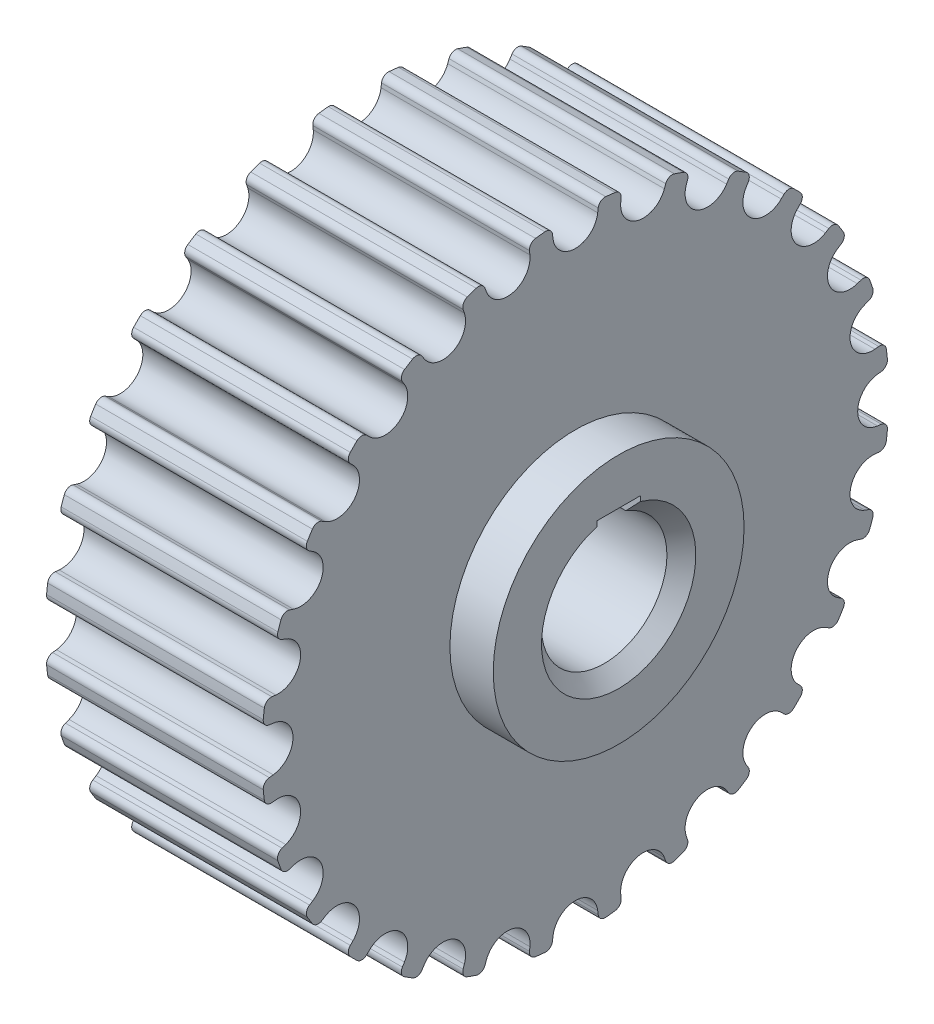
SolidWorks part; units mm, degrees
ref_plane "前视基准面" through (0, 0, 0) normal (0, 0, 1) x (1, 0, 0)
ref_plane "上视基准面" through (0, 0, 0) normal (0, 1, 0) x (1, 0, 0)
ref_plane "右视基准面" through (0, 0, 0) normal (1, 0, 0) x (0, 0, -1)
sketch "草图1" plane through (0, 0, 0) normal (0, 0, 1) x (1, 0, 0)
  line L0 (0, 0) -> (64.8368, 0) construction
  line L1 (0, 4.3416) -> (0, 21.708)
  line L2 (0, 21.708) -> (15, 21.708)
  line L3 (15, 21.708) -> (15, 8.6832)
  line L4 (15, 8.6832) -> (18, 8.6832)
  line L5 (18, 8.6832) -> (18, 4.3416)
  line L6 (18, 4.3416) -> (0, 4.3416)
  dimension "L" = 18
  dimension "B" = 15
  dimension "d" = 8.6832
  dimension "d1" = 17.3664
  dimension "da" = 43.416
revolve "旋转1" add sketch "草图1" angle 360 about L0
chamfer "倒角1" distance 1 angle 45 2 edges at (18, 0, 4.3416) (0, 0, 4.3416)
sketch "草图4" plane through (0, 0, 0) normal (-1, 0, 0) x (0, 0, 1)
  line L1 (-1.5, 4.0742) -> (1.5, 4.0742)
  line L2 (-1.5, 4.0742) -> (-1.5, 5.4742)
  line L3 (-1.5, 5.4742) -> (1.5, 5.4742)
  line L4 (1.5, 4.0742) -> (1.5, 5.4742)
  circle A0 centre (0, 0) radius 4.3416 construction
  dimension "键槽宽度" = 3
  dimension "t1" = 1.4
extrude "切除-拉伸1" cut sketch "草图4" against normal through all
ref_axis "基准轴1" through (-1.4, 0, 0) along (1, 0, 0)
sketch "草图6" plane through (0, 0, 0) normal (1, 0, 0) x (0, 0, -1)
  line L0 (0, 0) -> (0, 30.6512) construction
  line L1 (1.5814, 21.1865) -> (1.5484, 20.9179)
  line L2 (2.5815, 21.554) -> (2.7782, 23.1555)
  line L3 (-2.5815, 21.554) -> (-2.7782, 23.1555)
  line L4 (-1.5814, 21.1865) -> (-1.5484, 20.9179)
  circle A0 centre (0, 0) radius 21.708 construction
  circle A1 centre (0, 0) radius 19.548 construction
  arc A2 (-1.5484, 20.9179) -> (1.5484, 20.9179) centre (0, 21.108) ccw
  arc A3 (2.7782, 23.1555) -> (-2.7782, 23.1555) centre (0, 0) ccw
  arc A4 (1.5814, 21.1865) -> (2.1043, 21.6058) centre (2.0578, 21.128) cw
  arc A5 (2.1043, 21.6058) -> (2.5815, 21.554) centre (0, 0) cw
  arc A6 (-2.1043, 21.6058) -> (-2.5815, 21.554) centre (0, 0) ccw
  arc A7 (-1.5814, 21.1865) -> (-2.1043, 21.6058) centre (-2.0578, 21.128) ccw
  point P7 (0, 3.25)
  point P8 (0, 28.4912)
  point P15 (1.6378, 21.6461)
  dimension "D1" = 39.096
  dimension "ra" = 0.48
  dimension "rf" = 1.56
  dimension "hg" = 2.16
  dimension "D3" = 0.48
  dimension "D4" = 1.6136
  dimension "angle" = 14
  dimension "bw" = 3.25
extrude "切除-拉伸2" cut sketch "草图6" along normal up to next
pattern_circular "阵列(圆周)3" count 28 over 360 about axis through (-1.4, 0, 0) along (1, 0, 0) of "切除-拉伸2"
ref_plane "基准面1" through (45, 0, 0) normal (1, 0, 0) x (0, 0, -1)
sketch "草图7" plane through (45, 0, 0) normal (1, 0, 0) x (0, 0, -1)
  line L56 (1.5814, 21.1865) -> (1.5484, 20.9179)
  line L57 (-1.5484, 20.9179) -> (-1.5814, 21.1865)
  line L58 (-3.1727, 21.0072) -> (-3.1451, 20.738)
  line L59 (-6.1642, 20.0489) -> (-6.2562, 20.3034)
  line L60 (-7.7677, 19.7745) -> (-7.6809, 19.5182)
  line L61 (-10.471, 18.1745) -> (-10.6172, 18.4023)
  line L62 (-11.9732, 17.5503) -> (-11.8315, 17.3197)
  line L63 (-14.2527, 15.3889) -> (-14.4459, 15.5783)
  line L64 (-15.5783, 14.4459) -> (-15.3889, 14.2527)
  line L65 (-17.3197, 11.8315) -> (-17.5503, 11.9732)
  line L66 (-18.4023, 10.6172) -> (-18.1745, 10.471)
  line L67 (-19.5182, 7.6809) -> (-19.7745, 7.7677)
  line L68 (-20.3034, 6.2562) -> (-20.0489, 6.1642)
  line L69 (-20.738, 3.1451) -> (-21.0072, 3.1727)
  line L70 (-21.1865, 1.5814) -> (-20.9179, 1.5484)
  line L71 (-20.9179, -1.5484) -> (-21.1865, -1.5814)
  line L72 (-21.0072, -3.1727) -> (-20.738, -3.1451)
  line L73 (-20.0489, -6.1642) -> (-20.3034, -6.2562)
  line L74 (-19.7745, -7.7677) -> (-19.5182, -7.6809)
  line L75 (-18.1745, -10.471) -> (-18.4023, -10.6172)
  line L76 (-17.5503, -11.9732) -> (-17.3197, -11.8315)
  line L77 (-15.3889, -14.2527) -> (-15.5783, -14.4459)
  line L78 (-14.4459, -15.5783) -> (-14.2527, -15.3889)
  line L79 (-11.8315, -17.3197) -> (-11.9732, -17.5503)
  line L80 (-10.6172, -18.4023) -> (-10.471, -18.1745)
  line L81 (-7.6809, -19.5182) -> (-7.7677, -19.7745)
  line L82 (-6.2562, -20.3034) -> (-6.1642, -20.0489)
  line L83 (-3.1451, -20.738) -> (-3.1727, -21.0072)
  line L84 (-1.5814, -21.1865) -> (-1.5484, -20.9179)
  line L85 (1.5484, -20.9179) -> (1.5814, -21.1865)
  line L86 (3.1727, -21.0072) -> (3.1451, -20.738)
  line L87 (6.1642, -20.0489) -> (6.2562, -20.3034)
  line L88 (7.7677, -19.7745) -> (7.6809, -19.5182)
  line L89 (10.471, -18.1745) -> (10.6172, -18.4023)
  line L90 (11.9732, -17.5503) -> (11.8315, -17.3197)
  line L91 (14.2527, -15.3889) -> (14.4459, -15.5783)
  line L92 (15.5783, -14.4459) -> (15.3889, -14.2527)
  line L93 (17.3197, -11.8315) -> (17.5503, -11.9732)
  line L94 (18.4023, -10.6172) -> (18.1745, -10.471)
  line L95 (19.5182, -7.6809) -> (19.7745, -7.7677)
  line L96 (20.3034, -6.2562) -> (20.0489, -6.1642)
  line L97 (20.738, -3.1451) -> (21.0072, -3.1727)
  line L98 (21.1865, -1.5814) -> (20.9179, -1.5484)
  line L99 (20.9179, 1.5484) -> (21.1865, 1.5814)
  line L100 (21.0072, 3.1727) -> (20.738, 3.1451)
  line L101 (20.0489, 6.1642) -> (20.3034, 6.2562)
  line L102 (19.7745, 7.7677) -> (19.5182, 7.6809)
  line L103 (18.1745, 10.471) -> (18.4023, 10.6172)
  line L104 (17.5503, 11.9732) -> (17.3197, 11.8315)
  line L105 (15.3889, 14.2527) -> (15.5783, 14.4459)
  line L106 (14.4459, 15.5783) -> (14.2527, 15.3889)
  line L107 (11.8315, 17.3197) -> (11.9732, 17.5503)
  line L108 (10.6172, 18.4023) -> (10.471, 18.1745)
  line L109 (7.6809, 19.5182) -> (7.7677, 19.7745)
  line L110 (6.2562, 20.3034) -> (6.1642, 20.0489)
  line L111 (3.1451, 20.738) -> (3.1727, 21.0072)
  line L112 (1.5814, 21.1865) -> (1.5484, 20.9179)
  line L113 (-1.5484, 20.9179) -> (-1.5814, 21.1865)
  line L114 (-3.1727, 21.0072) -> (-3.1451, 20.738)
  line L115 (-6.1642, 20.0489) -> (-6.2562, 20.3034)
  line L116 (-7.7677, 19.7745) -> (-7.6809, 19.5182)
  line L117 (-10.471, 18.1745) -> (-10.6172, 18.4023)
  line L118 (-11.9732, 17.5503) -> (-11.8315, 17.3197)
  line L119 (-14.2527, 15.3889) -> (-14.4459, 15.5783)
  line L120 (-15.5783, 14.4459) -> (-15.3889, 14.2527)
  line L121 (-17.3197, 11.8315) -> (-17.5503, 11.9732)
  line L122 (-18.4023, 10.6172) -> (-18.1745, 10.471)
  line L123 (-19.5182, 7.6809) -> (-19.7745, 7.7677)
  line L124 (-20.3034, 6.2562) -> (-20.0489, 6.1642)
  line L125 (-20.738, 3.1451) -> (-21.0072, 3.1727)
  line L126 (-21.1865, 1.5814) -> (-20.9179, 1.5484)
  line L127 (-20.9179, -1.5484) -> (-21.1865, -1.5814)
  line L128 (-21.0072, -3.1727) -> (-20.738, -3.1451)
  line L129 (-20.0489, -6.1642) -> (-20.3034, -6.2562)
  line L130 (-19.7745, -7.7677) -> (-19.5182, -7.6809)
  line L131 (-18.1745, -10.471) -> (-18.4023, -10.6172)
  line L132 (-17.5503, -11.9732) -> (-17.3197, -11.8315)
  line L133 (-15.3889, -14.2527) -> (-15.5783, -14.4459)
  line L134 (-14.4459, -15.5783) -> (-14.2527, -15.3889)
  line L135 (-11.8315, -17.3197) -> (-11.9732, -17.5503)
  line L136 (-10.6172, -18.4023) -> (-10.471, -18.1745)
  line L137 (-7.6809, -19.5182) -> (-7.7677, -19.7745)
  line L138 (-6.2562, -20.3034) -> (-6.1642, -20.0489)
  line L139 (-3.1451, -20.738) -> (-3.1727, -21.0072)
  line L140 (-1.5814, -21.1865) -> (-1.5484, -20.9179)
  line L141 (1.5484, -20.9179) -> (1.5814, -21.1865)
  line L142 (3.1727, -21.0072) -> (3.1451, -20.738)
  line L143 (6.1642, -20.0489) -> (6.2562, -20.3034)
  line L144 (7.7677, -19.7745) -> (7.6809, -19.5182)
  line L145 (10.471, -18.1745) -> (10.6172, -18.4023)
  line L146 (11.9732, -17.5503) -> (11.8315, -17.3197)
  line L147 (14.2527, -15.3889) -> (14.4459, -15.5783)
  line L148 (15.5783, -14.4459) -> (15.3889, -14.2527)
  line L149 (17.3197, -11.8315) -> (17.5503, -11.9732)
  line L150 (18.4023, -10.6172) -> (18.1745, -10.471)
  line L151 (19.5182, -7.6809) -> (19.7745, -7.7677)
  line L152 (20.3034, -6.2562) -> (20.0489, -6.1642)
  line L153 (20.738, -3.1451) -> (21.0072, -3.1727)
  line L154 (21.1865, -1.5814) -> (20.9179, -1.5484)
  line L155 (20.9179, 1.5484) -> (21.1865, 1.5814)
  line L156 (21.0072, 3.1727) -> (20.738, 3.1451)
  line L157 (20.0489, 6.1642) -> (20.3034, 6.2562)
  line L158 (19.7745, 7.7677) -> (19.5182, 7.6809)
  line L159 (18.1745, 10.471) -> (18.4023, 10.6172)
  line L160 (17.5503, 11.9732) -> (17.3197, 11.8315)
  line L161 (15.3889, 14.2527) -> (15.5783, 14.4459)
  line L162 (14.4459, 15.5783) -> (14.2527, 15.3889)
  line L163 (11.8315, 17.3197) -> (11.9732, 17.5503)
  line L164 (10.6172, 18.4023) -> (10.471, 18.1745)
  line L165 (7.6809, 19.5182) -> (7.7677, 19.7745)
  line L166 (6.2562, 20.3034) -> (6.1642, 20.0489)
  line L167 (3.1451, 20.738) -> (3.1727, 21.0072)
  arc A112 (3.1727, 21.0072) -> (2.7562, 21.5323) centre (2.6952, 21.0562) ccw
  arc A113 (2.7562, 21.5323) -> (2.1043, 21.6058) centre (0, 0) ccw
  arc A114 (2.1043, 21.6058) -> (1.5814, 21.1865) centre (2.0578, 21.128) ccw
  arc A115 (-1.5484, 20.9179) -> (1.5484, 20.9179) centre (0, 21.108) ccw
  arc A116 (-1.5814, 21.1865) -> (-2.1043, 21.6058) centre (-2.0578, 21.128) ccw
  arc A117 (-2.1043, 21.6058) -> (-2.7562, 21.5323) centre (0, 0) ccw
  arc A118 (-2.7562, 21.5323) -> (-3.1727, 21.0072) centre (-2.6952, 21.0562) ccw
  arc A119 (-6.1642, 20.0489) -> (-3.1451, 20.738) centre (-4.697, 20.5788) ccw
  arc A120 (-6.2562, 20.3034) -> (-6.8593, 20.5958) centre (-6.7076, 20.1404) ccw
  arc A121 (-6.8593, 20.5958) -> (-7.4785, 20.3791) centre (0, 0) ccw
  arc A122 (-7.4785, 20.3791) -> (-7.7677, 19.7745) centre (-7.3131, 19.9285) ccw
  arc A123 (-10.471, 18.1745) -> (-7.6809, 19.5182) centre (-9.1584, 19.0177) ccw
  arc A124 (-10.6172, 18.4023) -> (-11.2703, 18.5531) centre (-11.0211, 18.1429) ccw
  arc A125 (-11.2703, 18.5531) -> (-11.8258, 18.2041) centre (0, 0) ccw
  arc A126 (-11.8258, 18.2041) -> (-11.9732, 17.5503) centre (-11.5643, 17.8016) ccw
  arc A127 (-14.2527, 15.3889) -> (-11.8315, 17.3197) centre (-13.1606, 16.5029) ccw
  arc A128 (-14.4459, 15.5783) -> (-15.1162, 15.5801) centre (-14.7819, 15.2356) ccw
  arc A129 (-15.1162, 15.5801) -> (-15.5801, 15.1162) centre (0, 0) ccw
  arc A130 (-15.5801, 15.1162) -> (-15.5783, 14.4459) centre (-15.2356, 14.7819) ccw
  arc A131 (-17.3197, 11.8315) -> (-15.3889, 14.2527) centre (-16.5029, 13.1606) ccw
  arc A132 (-17.5503, 11.9732) -> (-18.2041, 11.8258) centre (-17.8016, 11.5643) ccw
  arc A133 (-18.2041, 11.8258) -> (-18.5531, 11.2703) centre (0, 0) ccw
  arc A134 (-18.5531, 11.2703) -> (-18.4023, 10.6172) centre (-18.1429, 11.0211) ccw
  arc A135 (-19.5182, 7.6809) -> (-18.1745, 10.471) centre (-19.0177, 9.1584) ccw
  arc A136 (-19.7745, 7.7677) -> (-20.3791, 7.4785) centre (-19.9285, 7.3131) ccw
  arc A137 (-20.3791, 7.4785) -> (-20.5958, 6.8593) centre (0, 0) ccw
  arc A138 (-20.5958, 6.8593) -> (-20.3034, 6.2562) centre (-20.1404, 6.7076) ccw
  arc A139 (-20.738, 3.1451) -> (-20.0489, 6.1642) centre (-20.5788, 4.697) ccw
  arc A140 (-21.0072, 3.1727) -> (-21.5323, 2.7562) centre (-21.0562, 2.6952) ccw
  arc A141 (-21.5323, 2.7562) -> (-21.6058, 2.1043) centre (0, 0) ccw
  arc A142 (-21.6058, 2.1043) -> (-21.1865, 1.5814) centre (-21.128, 2.0578) ccw
  arc A143 (-20.9179, -1.5484) -> (-20.9179, 1.5484) centre (-21.108, 0) ccw
  arc A144 (-21.1865, -1.5814) -> (-21.6058, -2.1043) centre (-21.128, -2.0578) ccw
  arc A145 (-21.6058, -2.1043) -> (-21.5323, -2.7562) centre (0, 0) ccw
  arc A146 (-21.5323, -2.7562) -> (-21.0072, -3.1727) centre (-21.0562, -2.6952) ccw
  arc A147 (-20.0489, -6.1642) -> (-20.738, -3.1451) centre (-20.5788, -4.697) ccw
  arc A148 (-20.3034, -6.2562) -> (-20.5958, -6.8593) centre (-20.1404, -6.7076) ccw
  arc A149 (-20.5958, -6.8593) -> (-20.3791, -7.4785) centre (0, 0) ccw
  arc A150 (-20.3791, -7.4785) -> (-19.7745, -7.7677) centre (-19.9285, -7.3131) ccw
  arc A151 (-18.1745, -10.471) -> (-19.5182, -7.6809) centre (-19.0177, -9.1584) ccw
  arc A152 (-18.4023, -10.6172) -> (-18.5531, -11.2703) centre (-18.1429, -11.0211) ccw
  arc A153 (-18.5531, -11.2703) -> (-18.2041, -11.8258) centre (0, 0) ccw
  arc A154 (-18.2041, -11.8258) -> (-17.5503, -11.9732) centre (-17.8016, -11.5643) ccw
  arc A155 (-15.3889, -14.2527) -> (-17.3197, -11.8315) centre (-16.5029, -13.1606) ccw
  arc A156 (-15.5783, -14.4459) -> (-15.5801, -15.1162) centre (-15.2356, -14.7819) ccw
  arc A157 (-15.5801, -15.1162) -> (-15.1162, -15.5801) centre (0, 0) ccw
  arc A158 (-15.1162, -15.5801) -> (-14.4459, -15.5783) centre (-14.7819, -15.2356) ccw
  arc A159 (-11.8315, -17.3197) -> (-14.2527, -15.3889) centre (-13.1606, -16.5029) ccw
  arc A160 (-11.9732, -17.5503) -> (-11.8258, -18.2041) centre (-11.5643, -17.8016) ccw
  arc A161 (-11.8258, -18.2041) -> (-11.2703, -18.5531) centre (0, 0) ccw
  arc A162 (-11.2703, -18.5531) -> (-10.6172, -18.4023) centre (-11.0211, -18.1429) ccw
  arc A163 (-7.6809, -19.5182) -> (-10.471, -18.1745) centre (-9.1584, -19.0177) ccw
  arc A164 (-7.7677, -19.7745) -> (-7.4785, -20.3791) centre (-7.3131, -19.9285) ccw
  arc A165 (-7.4785, -20.3791) -> (-6.8593, -20.5958) centre (0, 0) ccw
  arc A166 (-6.8593, -20.5958) -> (-6.2562, -20.3034) centre (-6.7076, -20.1404) ccw
  arc A167 (-3.1451, -20.738) -> (-6.1642, -20.0489) centre (-4.697, -20.5788) ccw
  arc A168 (-3.1727, -21.0072) -> (-2.7562, -21.5323) centre (-2.6952, -21.0562) ccw
  arc A169 (-2.7562, -21.5323) -> (-2.1043, -21.6058) centre (0, 0) ccw
  arc A170 (-2.1043, -21.6058) -> (-1.5814, -21.1865) centre (-2.0578, -21.128) ccw
  arc A171 (1.5484, -20.9179) -> (-1.5484, -20.9179) centre (0, -21.108) ccw
  arc A172 (1.5814, -21.1865) -> (2.1043, -21.6058) centre (2.0578, -21.128) ccw
  arc A173 (2.1043, -21.6058) -> (2.7562, -21.5323) centre (0, 0) ccw
  arc A174 (2.7562, -21.5323) -> (3.1727, -21.0072) centre (2.6952, -21.0562) ccw
  arc A175 (6.1642, -20.0489) -> (3.1451, -20.738) centre (4.697, -20.5788) ccw
  arc A176 (6.2562, -20.3034) -> (6.8593, -20.5958) centre (6.7076, -20.1404) ccw
  arc A177 (6.8593, -20.5958) -> (7.4785, -20.3791) centre (0, 0) ccw
  arc A178 (7.4785, -20.3791) -> (7.7677, -19.7745) centre (7.3131, -19.9285) ccw
  arc A179 (10.471, -18.1745) -> (7.6809, -19.5182) centre (9.1584, -19.0177) ccw
  arc A180 (10.6172, -18.4023) -> (11.2703, -18.5531) centre (11.0211, -18.1429) ccw
  arc A181 (11.2703, -18.5531) -> (11.8258, -18.2041) centre (0, 0) ccw
  arc A182 (11.8258, -18.2041) -> (11.9732, -17.5503) centre (11.5643, -17.8016) ccw
  arc A183 (14.2527, -15.3889) -> (11.8315, -17.3197) centre (13.1606, -16.5029) ccw
  arc A184 (14.4459, -15.5783) -> (15.1162, -15.5801) centre (14.7819, -15.2356) ccw
  arc A185 (15.1162, -15.5801) -> (15.5801, -15.1162) centre (0, 0) ccw
  arc A186 (15.5801, -15.1162) -> (15.5783, -14.4459) centre (15.2356, -14.7819) ccw
  arc A187 (17.3197, -11.8315) -> (15.3889, -14.2527) centre (16.5029, -13.1606) ccw
  arc A188 (17.5503, -11.9732) -> (18.2041, -11.8258) centre (17.8016, -11.5643) ccw
  arc A189 (18.2041, -11.8258) -> (18.5531, -11.2703) centre (0, 0) ccw
  arc A190 (18.5531, -11.2703) -> (18.4023, -10.6172) centre (18.1429, -11.0211) ccw
  arc A191 (19.5182, -7.6809) -> (18.1745, -10.471) centre (19.0177, -9.1584) ccw
  arc A192 (19.7745, -7.7677) -> (20.3791, -7.4785) centre (19.9285, -7.3131) ccw
  arc A193 (20.3791, -7.4785) -> (20.5958, -6.8593) centre (0, 0) ccw
  arc A194 (20.5958, -6.8593) -> (20.3034, -6.2562) centre (20.1404, -6.7076) ccw
  arc A195 (20.738, -3.1451) -> (20.0489, -6.1642) centre (20.5788, -4.697) ccw
  arc A196 (21.0072, -3.1727) -> (21.5323, -2.7562) centre (21.0562, -2.6952) ccw
  arc A197 (21.5323, -2.7562) -> (21.6058, -2.1043) centre (0, 0) ccw
  arc A198 (21.6058, -2.1043) -> (21.1865, -1.5814) centre (21.128, -2.0578) ccw
  arc A199 (20.9179, 1.5484) -> (20.9179, -1.5484) centre (21.108, 0) ccw
  arc A200 (21.1865, 1.5814) -> (21.6058, 2.1043) centre (21.128, 2.0578) ccw
  arc A201 (21.6058, 2.1043) -> (21.5323, 2.7562) centre (0, 0) ccw
  arc A202 (21.5323, 2.7562) -> (21.0072, 3.1727) centre (21.0562, 2.6952) ccw
  arc A203 (20.0489, 6.1642) -> (20.738, 3.1451) centre (20.5788, 4.697) ccw
  arc A204 (20.3034, 6.2562) -> (20.5958, 6.8593) centre (20.1404, 6.7076) ccw
  arc A205 (20.5958, 6.8593) -> (20.3791, 7.4785) centre (0, 0) ccw
  arc A206 (20.3791, 7.4785) -> (19.7745, 7.7677) centre (19.9285, 7.3131) ccw
  arc A207 (18.1745, 10.471) -> (19.5182, 7.6809) centre (19.0177, 9.1584) ccw
  arc A208 (18.4023, 10.6172) -> (18.5531, 11.2703) centre (18.1429, 11.0211) ccw
  arc A209 (18.5531, 11.2703) -> (18.2041, 11.8258) centre (0, 0) ccw
  arc A210 (18.2041, 11.8258) -> (17.5503, 11.9732) centre (17.8016, 11.5643) ccw
  arc A211 (15.3889, 14.2527) -> (17.3197, 11.8315) centre (16.5029, 13.1606) ccw
  arc A212 (15.5783, 14.4459) -> (15.5801, 15.1162) centre (15.2356, 14.7819) ccw
  arc A213 (15.5801, 15.1162) -> (15.1162, 15.5801) centre (0, 0) ccw
  arc A214 (15.1162, 15.5801) -> (14.4459, 15.5783) centre (14.7819, 15.2356) ccw
  arc A215 (11.8315, 17.3197) -> (14.2527, 15.3889) centre (13.1606, 16.5029) ccw
  arc A216 (11.9732, 17.5503) -> (11.8258, 18.2041) centre (11.5643, 17.8016) ccw
  arc A217 (11.8258, 18.2041) -> (11.2703, 18.5531) centre (0, 0) ccw
  arc A218 (11.2703, 18.5531) -> (10.6172, 18.4023) centre (11.0211, 18.1429) ccw
  arc A219 (7.6809, 19.5182) -> (10.471, 18.1745) centre (9.1584, 19.0177) ccw
  arc A220 (7.7677, 19.7745) -> (7.4785, 20.3791) centre (7.3131, 19.9285) ccw
  arc A221 (7.4785, 20.3791) -> (6.8593, 20.5958) centre (0, 0) ccw
  arc A222 (6.8593, 20.5958) -> (6.2562, 20.3034) centre (6.7076, 20.1404) ccw
  arc A223 (3.1451, 20.738) -> (6.1642, 20.0489) centre (4.697, 20.5788) ccw
  arc A224 (3.1727, 21.0072) -> (2.7562, 21.5323) centre (2.6952, 21.0562) ccw
  arc A225 (2.7562, 21.5323) -> (2.1043, 21.6058) centre (0, 0) ccw
  arc A226 (2.1043, 21.6058) -> (1.5814, 21.1865) centre (2.0578, 21.128) ccw
  arc A227 (-1.5484, 20.9179) -> (1.5484, 20.9179) centre (0, 21.108) ccw
  arc A228 (-1.5814, 21.1865) -> (-2.1043, 21.6058) centre (-2.0578, 21.128) ccw
  arc A229 (-2.1043, 21.6058) -> (-2.7562, 21.5323) centre (0, 0) ccw
  arc A230 (-2.7562, 21.5323) -> (-3.1727, 21.0072) centre (-2.6952, 21.0562) ccw
  arc A231 (-6.1642, 20.0489) -> (-3.1451, 20.738) centre (-4.697, 20.5788) ccw
  arc A232 (-6.2562, 20.3034) -> (-6.8593, 20.5958) centre (-6.7076, 20.1404) ccw
  arc A233 (-6.8593, 20.5958) -> (-7.4785, 20.3791) centre (0, 0) ccw
  arc A234 (-7.4785, 20.3791) -> (-7.7677, 19.7745) centre (-7.3131, 19.9285) ccw
  arc A235 (-10.471, 18.1745) -> (-7.6809, 19.5182) centre (-9.1584, 19.0177) ccw
  arc A236 (-10.6172, 18.4023) -> (-11.2703, 18.5531) centre (-11.0211, 18.1429) ccw
  arc A237 (-11.2703, 18.5531) -> (-11.8258, 18.2041) centre (0, 0) ccw
  arc A238 (-11.8258, 18.2041) -> (-11.9732, 17.5503) centre (-11.5643, 17.8016) ccw
  arc A239 (-14.2527, 15.3889) -> (-11.8315, 17.3197) centre (-13.1606, 16.5029) ccw
  arc A240 (-14.4459, 15.5783) -> (-15.1162, 15.5801) centre (-14.7819, 15.2356) ccw
  arc A241 (-15.1162, 15.5801) -> (-15.5801, 15.1162) centre (0, 0) ccw
  arc A242 (-15.5801, 15.1162) -> (-15.5783, 14.4459) centre (-15.2356, 14.7819) ccw
  arc A243 (-17.3197, 11.8315) -> (-15.3889, 14.2527) centre (-16.5029, 13.1606) ccw
  arc A244 (-17.5503, 11.9732) -> (-18.2041, 11.8258) centre (-17.8016, 11.5643) ccw
  arc A245 (-18.2041, 11.8258) -> (-18.5531, 11.2703) centre (0, 0) ccw
  arc A246 (-18.5531, 11.2703) -> (-18.4023, 10.6172) centre (-18.1429, 11.0211) ccw
  arc A247 (-19.5182, 7.6809) -> (-18.1745, 10.471) centre (-19.0177, 9.1584) ccw
  arc A248 (-19.7745, 7.7677) -> (-20.3791, 7.4785) centre (-19.9285, 7.3131) ccw
  arc A249 (-20.3791, 7.4785) -> (-20.5958, 6.8593) centre (0, 0) ccw
  arc A250 (-20.5958, 6.8593) -> (-20.3034, 6.2562) centre (-20.1404, 6.7076) ccw
  arc A251 (-20.738, 3.1451) -> (-20.0489, 6.1642) centre (-20.5788, 4.697) ccw
  arc A252 (-21.0072, 3.1727) -> (-21.5323, 2.7562) centre (-21.0562, 2.6952) ccw
  arc A253 (-21.5323, 2.7562) -> (-21.6058, 2.1043) centre (0, 0) ccw
  arc A254 (-21.6058, 2.1043) -> (-21.1865, 1.5814) centre (-21.128, 2.0578) ccw
  arc A255 (-20.9179, -1.5484) -> (-20.9179, 1.5484) centre (-21.108, 0) ccw
  arc A256 (-21.1865, -1.5814) -> (-21.6058, -2.1043) centre (-21.128, -2.0578) ccw
  arc A257 (-21.6058, -2.1043) -> (-21.5323, -2.7562) centre (0, 0) ccw
  arc A258 (-21.5323, -2.7562) -> (-21.0072, -3.1727) centre (-21.0562, -2.6952) ccw
  arc A259 (-20.0489, -6.1642) -> (-20.738, -3.1451) centre (-20.5788, -4.697) ccw
  arc A260 (-20.3034, -6.2562) -> (-20.5958, -6.8593) centre (-20.1404, -6.7076) ccw
  arc A261 (-20.5958, -6.8593) -> (-20.3791, -7.4785) centre (0, 0) ccw
  arc A262 (-20.3791, -7.4785) -> (-19.7745, -7.7677) centre (-19.9285, -7.3131) ccw
  arc A263 (-18.1745, -10.471) -> (-19.5182, -7.6809) centre (-19.0177, -9.1584) ccw
  arc A264 (-18.4023, -10.6172) -> (-18.5531, -11.2703) centre (-18.1429, -11.0211) ccw
  arc A265 (-18.5531, -11.2703) -> (-18.2041, -11.8258) centre (0, 0) ccw
  arc A266 (-18.2041, -11.8258) -> (-17.5503, -11.9732) centre (-17.8016, -11.5643) ccw
  arc A267 (-15.3889, -14.2527) -> (-17.3197, -11.8315) centre (-16.5029, -13.1606) ccw
  arc A268 (-15.5783, -14.4459) -> (-15.5801, -15.1162) centre (-15.2356, -14.7819) ccw
  arc A269 (-15.5801, -15.1162) -> (-15.1162, -15.5801) centre (0, 0) ccw
  arc A270 (-15.1162, -15.5801) -> (-14.4459, -15.5783) centre (-14.7819, -15.2356) ccw
  arc A271 (-11.8315, -17.3197) -> (-14.2527, -15.3889) centre (-13.1606, -16.5029) ccw
  arc A272 (-11.9732, -17.5503) -> (-11.8258, -18.2041) centre (-11.5643, -17.8016) ccw
  arc A273 (-11.8258, -18.2041) -> (-11.2703, -18.5531) centre (0, 0) ccw
  arc A274 (-11.2703, -18.5531) -> (-10.6172, -18.4023) centre (-11.0211, -18.1429) ccw
  arc A275 (-7.6809, -19.5182) -> (-10.471, -18.1745) centre (-9.1584, -19.0177) ccw
  arc A276 (-7.7677, -19.7745) -> (-7.4785, -20.3791) centre (-7.3131, -19.9285) ccw
  arc A277 (-7.4785, -20.3791) -> (-6.8593, -20.5958) centre (0, 0) ccw
  arc A278 (-6.8593, -20.5958) -> (-6.2562, -20.3034) centre (-6.7076, -20.1404) ccw
  arc A279 (-3.1451, -20.738) -> (-6.1642, -20.0489) centre (-4.697, -20.5788) ccw
  arc A280 (-3.1727, -21.0072) -> (-2.7562, -21.5323) centre (-2.6952, -21.0562) ccw
  arc A281 (-2.7562, -21.5323) -> (-2.1043, -21.6058) centre (0, 0) ccw
  arc A282 (-2.1043, -21.6058) -> (-1.5814, -21.1865) centre (-2.0578, -21.128) ccw
  arc A283 (1.5484, -20.9179) -> (-1.5484, -20.9179) centre (0, -21.108) ccw
  arc A284 (1.5814, -21.1865) -> (2.1043, -21.6058) centre (2.0578, -21.128) ccw
  arc A285 (2.1043, -21.6058) -> (2.7562, -21.5323) centre (0, 0) ccw
  arc A286 (2.7562, -21.5323) -> (3.1727, -21.0072) centre (2.6952, -21.0562) ccw
  arc A287 (6.1642, -20.0489) -> (3.1451, -20.738) centre (4.697, -20.5788) ccw
  arc A288 (6.2562, -20.3034) -> (6.8593, -20.5958) centre (6.7076, -20.1404) ccw
  arc A289 (6.8593, -20.5958) -> (7.4785, -20.3791) centre (0, 0) ccw
  arc A290 (7.4785, -20.3791) -> (7.7677, -19.7745) centre (7.3131, -19.9285) ccw
  arc A291 (10.471, -18.1745) -> (7.6809, -19.5182) centre (9.1584, -19.0177) ccw
  arc A292 (10.6172, -18.4023) -> (11.2703, -18.5531) centre (11.0211, -18.1429) ccw
  arc A293 (11.2703, -18.5531) -> (11.8258, -18.2041) centre (0, 0) ccw
  arc A294 (11.8258, -18.2041) -> (11.9732, -17.5503) centre (11.5643, -17.8016) ccw
  arc A295 (14.2527, -15.3889) -> (11.8315, -17.3197) centre (13.1606, -16.5029) ccw
  arc A296 (14.4459, -15.5783) -> (15.1162, -15.5801) centre (14.7819, -15.2356) ccw
  arc A297 (15.1162, -15.5801) -> (15.5801, -15.1162) centre (0, 0) ccw
  arc A298 (15.5801, -15.1162) -> (15.5783, -14.4459) centre (15.2356, -14.7819) ccw
  arc A299 (17.3197, -11.8315) -> (15.3889, -14.2527) centre (16.5029, -13.1606) ccw
  arc A300 (17.5503, -11.9732) -> (18.2041, -11.8258) centre (17.8016, -11.5643) ccw
  arc A301 (18.2041, -11.8258) -> (18.5531, -11.2703) centre (0, 0) ccw
  arc A302 (18.5531, -11.2703) -> (18.4023, -10.6172) centre (18.1429, -11.0211) ccw
  arc A303 (19.5182, -7.6809) -> (18.1745, -10.471) centre (19.0177, -9.1584) ccw
  arc A304 (19.7745, -7.7677) -> (20.3791, -7.4785) centre (19.9285, -7.3131) ccw
  arc A305 (20.3791, -7.4785) -> (20.5958, -6.8593) centre (0, 0) ccw
  arc A306 (20.5958, -6.8593) -> (20.3034, -6.2562) centre (20.1404, -6.7076) ccw
  arc A307 (20.738, -3.1451) -> (20.0489, -6.1642) centre (20.5788, -4.697) ccw
  arc A308 (21.0072, -3.1727) -> (21.5323, -2.7562) centre (21.0562, -2.6952) ccw
  arc A309 (21.5323, -2.7562) -> (21.6058, -2.1043) centre (0, 0) ccw
  arc A310 (21.6058, -2.1043) -> (21.1865, -1.5814) centre (21.128, -2.0578) ccw
  arc A311 (20.9179, 1.5484) -> (20.9179, -1.5484) centre (21.108, 0) ccw
  arc A312 (21.1865, 1.5814) -> (21.6058, 2.1043) centre (21.128, 2.0578) ccw
  arc A313 (21.6058, 2.1043) -> (21.5323, 2.7562) centre (0, 0) ccw
  arc A314 (21.5323, 2.7562) -> (21.0072, 3.1727) centre (21.0562, 2.6952) ccw
  arc A315 (20.0489, 6.1642) -> (20.738, 3.1451) centre (20.5788, 4.697) ccw
  arc A316 (20.3034, 6.2562) -> (20.5958, 6.8593) centre (20.1404, 6.7076) ccw
  arc A317 (20.5958, 6.8593) -> (20.3791, 7.4785) centre (0, 0) ccw
  arc A318 (20.3791, 7.4785) -> (19.7745, 7.7677) centre (19.9285, 7.3131) ccw
  arc A319 (18.1745, 10.471) -> (19.5182, 7.6809) centre (19.0177, 9.1584) ccw
  arc A320 (18.4023, 10.6172) -> (18.5531, 11.2703) centre (18.1429, 11.0211) ccw
  arc A321 (18.5531, 11.2703) -> (18.2041, 11.8258) centre (0, 0) ccw
  arc A322 (18.2041, 11.8258) -> (17.5503, 11.9732) centre (17.8016, 11.5643) ccw
  arc A323 (15.3889, 14.2527) -> (17.3197, 11.8315) centre (16.5029, 13.1606) ccw
  arc A324 (15.5783, 14.4459) -> (15.5801, 15.1162) centre (15.2356, 14.7819) ccw
  arc A325 (15.5801, 15.1162) -> (15.1162, 15.5801) centre (0, 0) ccw
  arc A326 (15.1162, 15.5801) -> (14.4459, 15.5783) centre (14.7819, 15.2356) ccw
  arc A327 (11.8315, 17.3197) -> (14.2527, 15.3889) centre (13.1606, 16.5029) ccw
  arc A328 (11.9732, 17.5503) -> (11.8258, 18.2041) centre (11.5643, 17.8016) ccw
  arc A329 (11.8258, 18.2041) -> (11.2703, 18.5531) centre (0, 0) ccw
  arc A330 (11.2703, 18.5531) -> (10.6172, 18.4023) centre (11.0211, 18.1429) ccw
  arc A331 (7.6809, 19.5182) -> (10.471, 18.1745) centre (9.1584, 19.0177) ccw
  arc A332 (7.7677, 19.7745) -> (7.4785, 20.3791) centre (7.3131, 19.9285) ccw
  arc A333 (7.4785, 20.3791) -> (6.8593, 20.5958) centre (0, 0) ccw
  arc A334 (6.8593, 20.5958) -> (6.2562, 20.3034) centre (6.7076, 20.1404) ccw
  arc A335 (3.1451, 20.738) -> (6.1642, 20.0489) centre (4.697, 20.5788) ccw
  dimension "D1" = 0
equation "\"D1@草图6\" = \"da@草图1\"  - \"hg@草图6\" - \"hg@草图6\""
equation "\"D3@草图6\" = \"ra@草图6\""
